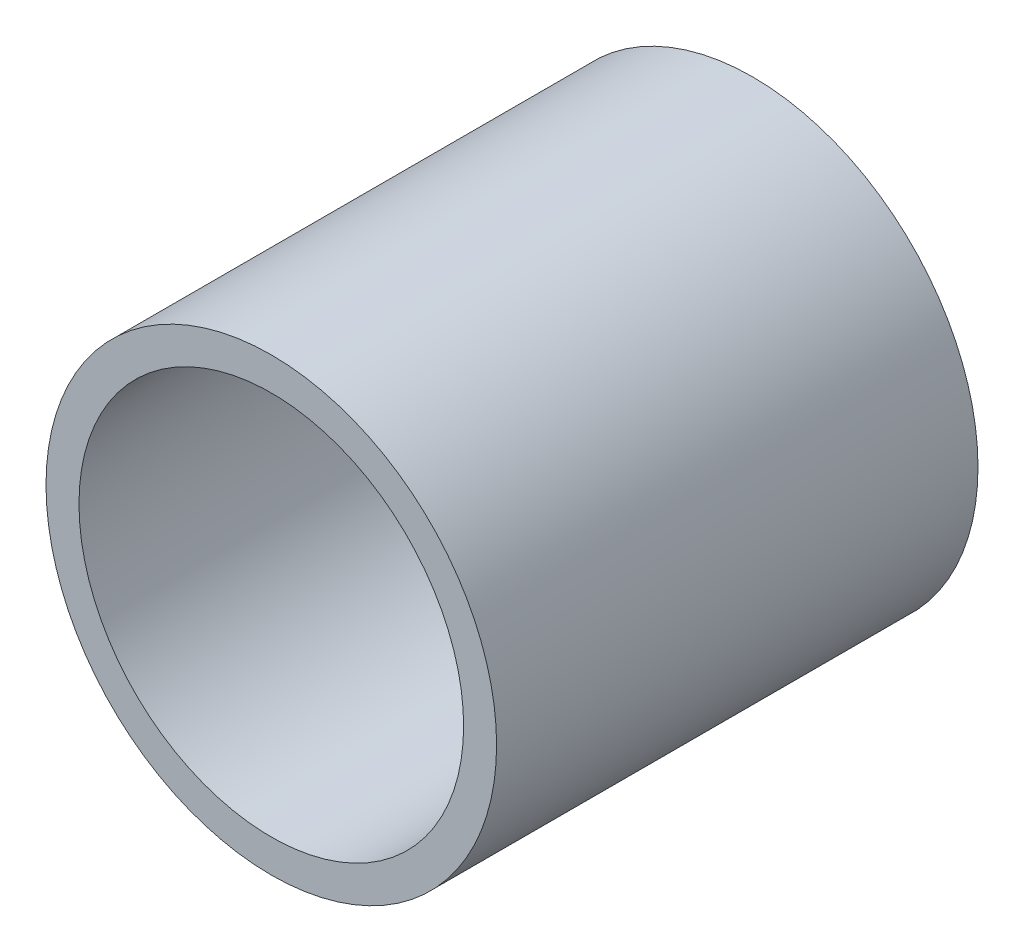
SolidWorks part; units mm, degrees
ref_plane "Front" through (0, 0, 0) normal (0, 0, 1) x (1, 0, 0)
ref_plane "Top" through (0, 0, 0) normal (0, 1, 0) x (1, 0, 0)
ref_plane "Right" through (0, 0, 0) normal (1, 0, 0) x (0, 0, -1)
sketch "Sketch1" plane through (0, 0, 0) normal (0, 0, 1) x (1, 0, 0)
  circle A0 centre (0, 0) radius 9.36
  circle A1 centre (0, 0) radius 7.99
extrude "Extrude1" add sketch "Sketch1" along normal blind 20
